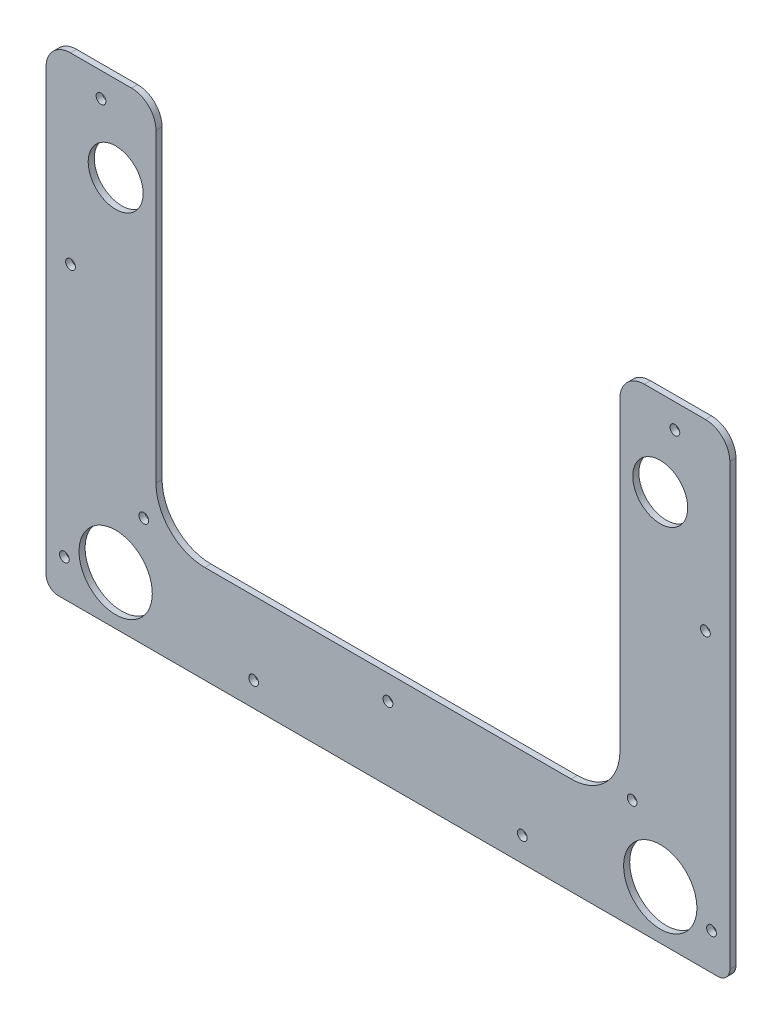
SolidWorks part; units mm, degrees
ref_plane "Front Plane" through (0, 0, 0) normal (0, 0, 1) x (1, 0, 0)
ref_plane "Top Plane" through (0, 0, 0) normal (0, 1, 0) x (1, 0, 0)
ref_plane "Right Plane" through (0, 0, 0) normal (1, 0, 0) x (0, 0, -1)
sketch "Sketch1" plane through (0, 0, 0) normal (0, 0, 1) x (1, 0, 0)
  line L5 (120.65, -152.4) -> (120.65, -6.35)
  line L6 (127, 0) -> (171.45, 0) construction
  line L7 (177.8, -6.35) -> (177.8, -222.25)
  line L10 (0, -206.2199) -> (0, -63.6275) construction
  line L11 (-54.9244, 0) -> (300.6756, 0) construction
  line L13 (12.7, -177.8) -> (95.25, -177.8)
  line L14 (12.7, -228.6) -> (171.45, -228.6)
  line L15 (141.605, -25.4) -> (141.605, -84.2822) construction
  line L16 (141.605, -25.4) -> (141.605, -127) construction
  line L19 (-141.605, -19.05) -> (-141.605, -77.9322) construction
  line L20 (141.605, -25.4) -> (141.605, -203.2) construction
  line L22 (-120.65, -152.4) -> (-120.65, -6.35)
  line L23 (-12.7, -177.8) -> (-95.25, -177.8)
  line L24 (-12.7, -228.6) -> (-171.45, -228.6)
  line L25 (-177.8, -6.35) -> (-177.8, -222.25)
  line L26 (-12.7, -177.8) -> (12.7, -177.8)
  line L27 (-12.7, -228.6) -> (12.7, -228.6)
  line L28 (-177.8, -6.35) -> (-177.8, 6.35)
  line L29 (-165.1, 19.05) -> (-133.35, 19.05)
  line L30 (-120.65, 6.35) -> (-120.65, -6.35)
  line L31 (120.65, 6.35) -> (120.65, -6.35)
  line L32 (177.8, -6.35) -> (177.8, 6.35)
  line L33 (165.1, 19.05) -> (133.35, 19.05)
  arc A0 (95.25, -177.8) -> (120.65, -152.4) centre (95.25, -152.4) ccw
  arc A4 (120.65, -6.35) -> (127, 0) centre (127, -6.35) cw construction
  circle A8 centre (141.605, -25.4) radius 14.2875
  circle A9 centre (141.605, -25.4) radius 38.1 construction
  arc A10 (177.8, -6.35) -> (171.45, 0) centre (171.45, -6.35) ccw construction
  arc A11 (171.45, -228.6) -> (177.8, -222.25) centre (171.45, -222.25) ccw
  arc A14 (141.605, -82.55) -> (120.9214, -78.6758) centre (141.605, -25.4) ccw construction
  arc A15 (-141.605, -82.55) -> (-120.9214, -78.6758) centre (-141.605, -25.4) cw construction
  circle A16 centre (-141.605, -25.4) radius 38.1 construction
  circle A17 centre (-141.605, -25.4) radius 14.2875
  arc A19 (-95.25, -177.8) -> (-120.65, -152.4) centre (-95.25, -152.4) cw
  circle A20 centre (141.605, -127) radius 38.1 construction
  circle A21 centre (-141.605, -127) radius 38.1 construction
  arc A23 (-171.45, -228.6) -> (-177.8, -222.25) centre (-171.45, -222.25) cw
  circle A24 centre (-141.605, -203.2) radius 19.05
  circle A37 centre (141.605, -203.2) radius 19.05
  circle A39 centre (-69.85, -215.9) radius 2.54
  circle A40 centre (69.85, -215.9) radius 2.54
  circle A42 centre (0, -190.5) radius 2.54
  arc A44 (-133.35, 19.05) -> (-120.65, 6.35) centre (-133.35, 6.35) cw
  arc A45 (-177.8, 6.35) -> (-165.1, 19.05) centre (-165.1, 6.35) cw
  arc A46 (133.35, 19.05) -> (120.65, 6.35) centre (133.35, 6.35) ccw
  arc A47 (177.8, 6.35) -> (165.1, 19.05) centre (165.1, 6.35) ccw
  circle A50 centre (-149.225, 6.35) radius 2.54
  circle A53 centre (149.225, 6.35) radius 2.54
  circle A54 centre (-168.275, -209.55) radius 2.54
  circle A56 centre (168.275, -209.55) radius 2.54
  circle A58 centre (-165.1, -76.2) radius 2.54
  circle A59 centre (165.1, -76.2) radius 2.54
  circle A60 centre (-127, -171.45) radius 2.54
  circle A61 centre (127, -171.45) radius 2.54
  point P2 (177.8, -44.45)
  point P18 (177.8, 0)
  point P23 (177.8, -228.6)
  point P24 (177.8, -228.6)
  point P25 (-127.9492, -143.3572)
  point P31 (177.8, 0)
  point P38 (-156.9827, -146.05)
  point P48 (-177.8, 0)
  point P49 (-177.8, -228.6)
  point P51 (-177.8, -44.45)
  point P64 (-128.2626, -152.4)
  point P71 (0, 0)
  point P72 (-165.1, -82.55)
  point P78 (-141.605, -203.2)
  dimension "D6" = 25.4
  dimension "D7" = 6.35
  dimension "D8" = 6.35
  dimension "D9" = 177.8
  dimension "D10" = 28.575
  dimension "D12" = 76.2
  dimension "D13" = 57.15
  dimension "D15" = 38.1
  dimension "D18" = 76.2
  dimension "D21" = 5.08
  dimension "D29" = 9.525
  dimension "D32" = 5.08
  dimension "D35" = 5.08
  dimension "D40" = 12.7
  dimension "D43" = 5.08
  dimension "D45" = 12.7
  dimension "D30" = 5.08
  dimension "D41" = 5.08
  dimension "D22" = 6.35
  dimension "D2" = 120.65
  dimension "D3" = 177.8
  dimension "D4" = 228.6
  dimension "D5" = 177.8
  dimension "D11" = 20.955
  dimension "`" = 25.4
  dimension "D14" = 57.15
  dimension "D16" = 184.15
  dimension "D17" = 101.6
  dimension "D19" = 25.4
  dimension "D20" = 107.95
  dimension "D23" = 57.15
  dimension "D26" = 19.05
  dimension "D27" = 25.4
  dimension "D28" = 25.4
  dimension "D33" = 12.7
  dimension "D34" = 12.7
  dimension "D36" = 12.7
  dimension "D39" = 19.05
  dimension "D44" = 28.575
  dimension "D24" = 95.25
extrude "Boss-Extrude3" add sketch "Sketch1" along normal blind 3.175
